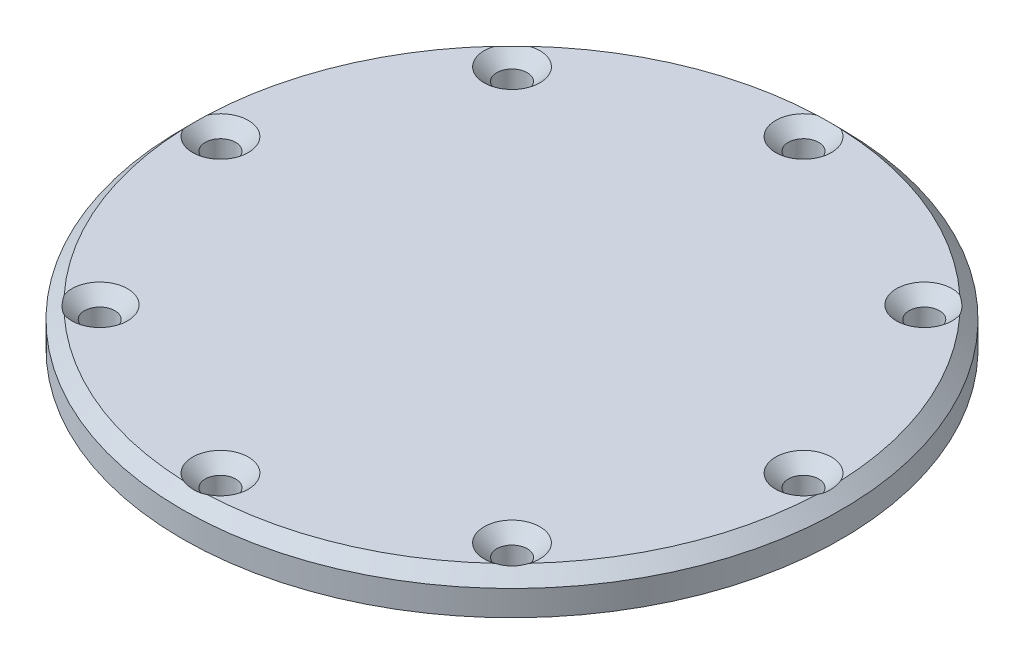
SolidWorks part; units mm, degrees
material "ПК/АБС"
ref_plane "Спереди" through (0, 0, 0) normal (0, 0, 1) x (1, 0, 0)
ref_plane "Сверху" through (0, 0, 0) normal (0, 1, 0) x (1, 0, 0)
ref_plane "Справа" through (0, 0, 0) normal (1, 0, 0) x (0, 0, -1)
sketch "Эскиз1" plane through (0, 0, 0) normal (0, 0, 1) x (1, 0, 0)
  line L0 (0, 0) -> (0, 14224.778) construction
  line L1 (0, 0) -> (26, 0)
  line L2 (26, 0) -> (26, 2)
  line L3 (26, 2) -> (25, 3)
  line L4 (25, 3) -> (0, 3)
  line L5 (0, 3) -> (0, 0)
  dimension "D1" = 3
  dimension "D2" = 52
  dimension "D3" = 1
  dimension "D4" = 45
revolve "Повернуть1" add sketch "Эскиз1" angle 360 about L0
hole_wizard "Зенковка для винта с потайной головкой M21" positions "Эскиз2" profile "Эскиз3" countersink size "M2" standard "HASCO Metric" end condition through all
sketch "Эскиз2" plane through (0, 3, 0) normal (0, 1, 0) x (1, 0, 0)
  line L2 (0, 0) -> (18.3848, 18.3848) construction
  line L4 (0, 0) -> (0, 26) construction
  circle A1 centre (0, 0) radius 26 construction
  circle A2 centre (0, 0) radius 23 construction
  point P0 (16.2635, 16.2635)
  dimension "D2" = 46
  dimension "D1" = 45
sketch "Эскиз3" plane through (16.2635, 3, -16.2635) normal (1, 0, 0) x (0, 0, 1)
  line L0 (0, 0) -> (0, 3)
  line L1 (0, 3) -> (1.2, 3)
  line L2 (1.2, 3) -> (1.2, 1)
  line L3 (1.2, 1) -> (2.2, 0)
  line L5 (2.2, 0) -> (0, 0)
  line L6 (-1.2, 1) -> (-2.2, 0) construction
  line L11 (0, -6.35) -> (0, 107.95) construction
  dimension "Диаметр сквозного отверстия" = 2.4
  dimension "Глубина сквозного отверстия" = 3
  dimension "Диаметр передней зенковки" = 4.4
  dimension "Угол передней зенковки" = 90
pattern_circular "Круговой массив1" count 8 over 360 about axis through (0, 0, 0) along (0, -1, 0) of "Зенковка для винта с потайной головкой M21" reverse direction yes
